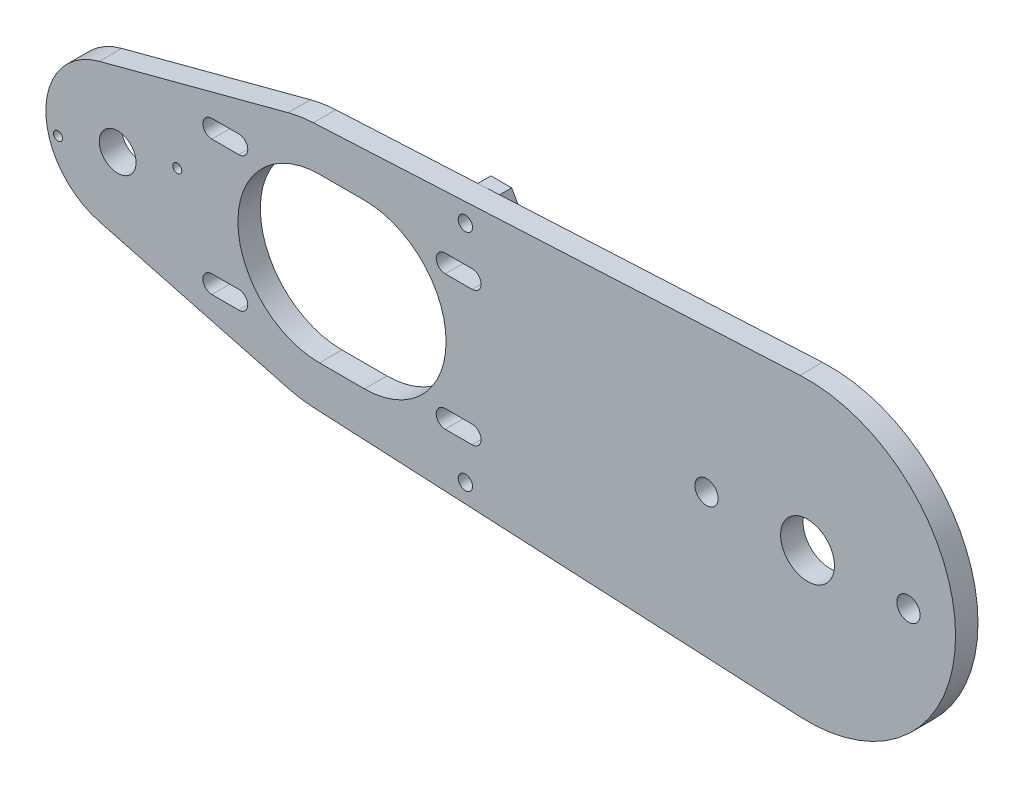
SolidWorks part; units mm, degrees
ref_plane "Front Plane" through (0, 0, 0) normal (0, 0, 1) x (1, 0, 0)
ref_plane "Top Plane" through (0, 0, 0) normal (0, 1, 0) x (1, 0, 0)
ref_plane "Right Plane" through (0, 0, 0) normal (1, 0, 0) x (0, 0, -1)
sketch "Sketch1" plane through (0, 0, 0) normal (0, 0, 1) x (1, 0, 0)
  line L0 (-51.875, 0) -> (51.875, 0) construction
  line L3 (-58.2658, 27.4648) -> (50.206, 32.9578)
  line L4 (-58.2658, -27.4648) -> (50.206, -32.9578)
  line L5 (-46.875, 0) -> (-56.875, 0) construction
  line L6 (-46.875, -18.2) -> (-56.875, -18.2)
  line L7 (-46.875, 18.2) -> (-56.875, 18.2)
  line L8 (-51.875, 0) -> (-101.875, 0) construction
  line L9 (-105.9639, 15.4687) -> (-63.9028, 26.5868)
  line L10 (-105.9639, -15.4687) -> (-63.9028, -26.5868)
  arc A3 (50.206, -32.9578) -> (50.206, 32.9578) centre (51.875, 0) ccw
  circle A5 centre (51.875, 0) radius 6
  arc A6 (-46.875, -18.2) -> (-46.875, 18.2) centre (-46.875, 0) ccw
  arc A7 (-56.875, 18.2) -> (-56.875, -18.2) centre (-56.875, 0) ccw
  arc A8 (-58.2658, 27.4648) -> (-63.9028, 26.5868) centre (-56.875, 0) ccw
  arc A9 (-105.9639, 15.4687) -> (-105.9639, -15.4687) centre (-101.875, 0) ccw
  circle A10 centre (-101.875, 0) radius 4.1
  arc A11 (-63.9028, -26.5868) -> (-58.2658, -27.4648) centre (-56.875, 0) ccw
  point P9 (-51.875, 0)
  point P16 (0, 0)
  point P23 (0, 0)
  dimension "D2" = 66
  dimension "D3" = 32
  dimension "D5" = 12
  dimension "D7" = 18.2
  dimension "D8" = 55
  dimension "D9" = 8.2
  dimension "D4" = 51.875
  dimension "D6" = 10
  dimension "D10" = 50
  dimension "D11" = 103.75
extrude "Boss-Extrude1" add sketch "Sketch1" along normal blind 5 contours L9 A9 L10 A8 A10 | L3 A8 L4 A3 A5 A7 L7 A6 L6 region at (-2.2766, 0, 0)
sketch "Sketch7" plane through (0, 0, 5) normal (0, 0, 1) x (1, 0, 0)
  line L0 (51.875, 5) -> (51.875, -5) construction
  line L1 (51.875, 0) -> (29.375, 0) construction
  circle A0 centre (51.875, 0) radius 5 construction
  circle A1 centre (29.375, 0) radius 2.6
  circle A2 centre (74.375, 0) radius 2.6
  dimension "D1" = 5.2
  dimension "D2" = 22.5
extrude "Cut-Extrude1" cut sketch "Sketch7" against normal blind 7
sketch "Sketch8" plane through (0, 0, 5) normal (0, 0, 1) x (1, 0, 0)
  line L0 (-84.375, 0) -> (-24.375, 0) construction
  line L1 (-24.375, 0) -> (-24.375, 25) construction
  line L3 (-28.9938, 25) -> (-26.6844, 21)
  line L4 (-26.6844, 21) -> (-22.0656, 21)
  line L5 (-22.0656, 21) -> (-19.7562, 25)
  line L6 (-19.7562, 25) -> (-22.0656, 29)
  line L7 (-22.0656, 29) -> (-26.6844, 29)
  line L8 (-26.6844, 29) -> (-28.9938, 25)
  line L9 (-25.775, 27.4249) -> (-27.175, 25)
  line L10 (-27.175, 25) -> (-25.775, 22.5751)
  line L11 (-25.775, 22.5751) -> (-22.975, 22.5751)
  line L12 (-22.975, 22.5751) -> (-21.575, 25)
  line L13 (-21.575, 25) -> (-22.975, 27.4249)
  line L14 (-22.975, 27.4249) -> (-25.775, 27.4249)
  arc A0 (-58.2658, 27.4648) -> (-58.2658, -27.4648) centre (-56.875, 0) ccw construction
  circle A2 centre (-24.375, 25) radius 4 construction
  circle A3 centre (-24.375, 25) radius 2.4249 construction
  point P6 (-24.375, 21)
  dimension "D1" = 8
  dimension "D2" = 5.6
  dimension "D3" = 25
  dimension "D4" = 60
extrude "Boss-Extrude7" add sketch "Sketch8" against normal blind 8
sketch "Sketch9" plane through (0, 0, 5) normal (0, 0, 1) x (1, 0, 0)
  line L0 (-24.375, 27.4249) -> (-24.375, 22.5751) construction
  line L1 (-22.975, 27.4249) -> (-25.775, 27.4249) construction
  line L2 (-25.775, 22.5751) -> (-22.975, 22.5751) construction
  circle A0 centre (-24.375, 25) radius 1.6
  dimension "D1" = 3.2
extrude "Cut-Extrude2" cut sketch "Sketch9" against normal blind 7
mirror "Mirror1" about plane through (0, 0, 0) normal (0, 1, 0) of "Boss-Extrude7"
mirror "Mirror2" about plane through (0, 0, 0) normal (0, 1, 0) of "Cut-Extrude2"
sketch "Sketch10" plane through (0, 0, 5) normal (0, 0, 1) x (1, 0, 0)
  line L0 (-51.875, 18.2) -> (-51.875, -18.2) construction
  line L1 (-46.875, 18.2) -> (-56.875, 18.2) construction
  line L2 (-46.875, -18.2) -> (-56.875, -18.2) construction
  line L3 (-80.875, 15) -> (-74.875, 15) construction
  line L6 (-25.875, -15) -> (-77.875, -15) construction
  line L7 (-25.875, -15) -> (-25.875, 15) construction
  line L10 (-25.875, 15) -> (-77.875, 15) construction
  line L13 (-77.875, -15) -> (-77.875, 15) construction
  line L14 (-25.875, -15) -> (-77.875, 15) construction
  line L15 (-25.875, 15) -> (-77.875, -15) construction
  line L16 (-80.875, 17) -> (-74.875, 17)
  line L17 (-80.875, 13) -> (-74.875, 13)
  line L18 (-51.875, 0) -> (-77.875, 0) construction
  line L19 (-22.875, 15) -> (-28.875, 15) construction
  line L20 (-22.875, 17) -> (-28.875, 17)
  line L21 (-22.875, 13) -> (-28.875, 13)
  line L22 (-22.875, -15) -> (-28.875, -15) construction
  line L23 (-22.875, -17) -> (-28.875, -17)
  line L24 (-22.875, -13) -> (-28.875, -13)
  line L25 (-80.875, -15) -> (-74.875, -15) construction
  line L26 (-80.875, -17) -> (-74.875, -17)
  line L27 (-80.875, -13) -> (-74.875, -13)
  arc A7 (-80.875, 17) -> (-80.875, 13) centre (-80.875, 15) ccw
  arc A8 (-74.875, 13) -> (-74.875, 17) centre (-74.875, 15) ccw
  arc A9 (-22.875, 17) -> (-22.875, 13) centre (-22.875, 15) cw
  arc A10 (-28.875, 13) -> (-28.875, 17) centre (-28.875, 15) cw
  arc A11 (-22.875, -17) -> (-22.875, -13) centre (-22.875, -15) ccw
  arc A12 (-28.875, -13) -> (-28.875, -17) centre (-28.875, -15) ccw
  arc A13 (-80.875, -17) -> (-80.875, -13) centre (-80.875, -15) cw
  arc A14 (-74.875, -13) -> (-74.875, -17) centre (-74.875, -15) cw
  point P6 (-51.875, 0)
  point P13 (-77.875, 15)
  point P23 (-25.875, 15)
  point P30 (-25.875, -15)
  point P37 (-77.875, -15)
  dimension "D1" = 52
  dimension "D2" = 30
  dimension "D3" = 2
  dimension "D4" = 6
extrude "Cut-Extrude3" cut sketch "Sketch10" against normal blind 10 contours L17 A8 L16 A7 | A14 L27 A13 L26 | L24 A12 L23 A11 | A10 L21 A9 L20
sketch "Sketch11" plane through (0, 0, 5) normal (0, 0, 1) x (1, 0, 0)
  line L0 (-101.875, 0) -> (-117.875, 0) construction
  line L1 (-101.875, 0) -> (-115.1682, -3.5147) construction
  line L2 (-101.875, 0) -> (-105.3897, 13.2932) construction
  arc A0 (-105.9639, 15.4687) -> (-105.9639, -15.4687) centre (-101.875, 0) ccw construction
  circle A1 centre (-101.875, 0) radius 13.75 construction
  circle A2 centre (-115.1682, -3.5147) radius 1
  circle A3 centre (-88.5818, 3.5147) radius 1
  dimension "D1" = 27.5
  dimension "D2" = 2
  dimension "D3" = 14.81
extrude "Cut-Extrude4" cut sketch "Sketch11" against normal blind 10
